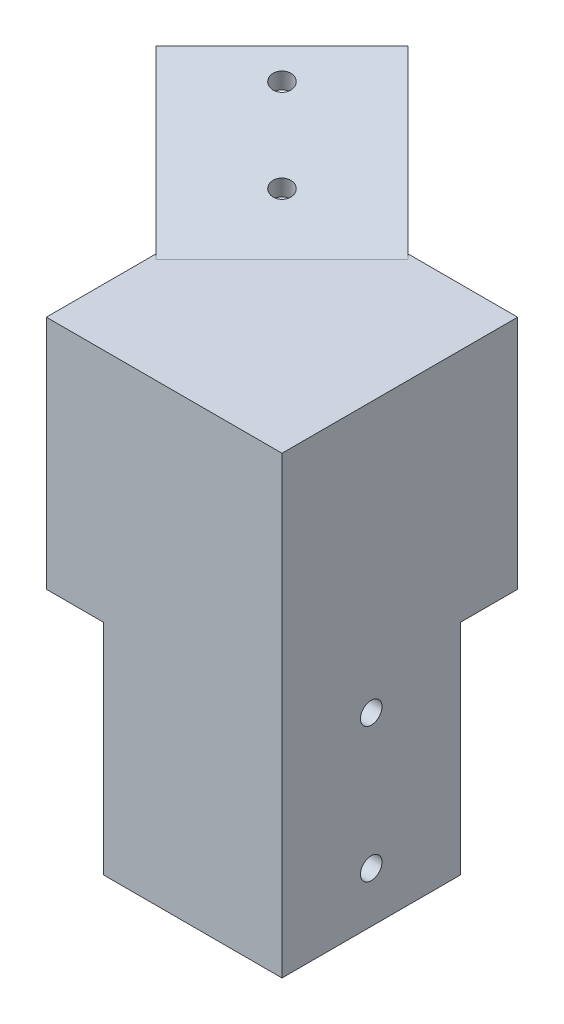
SolidWorks part; units mm, degrees
ref_plane "前视基准面" through (0, 0, 0) normal (0, 0, 1) x (1, 0, 0)
ref_plane "上视基准面" through (0, 0, 0) normal (0, 1, 0) x (1, 0, 0)
ref_plane "右视基准面" through (0, 0, 0) normal (1, 0, 0) x (0, 0, -1)
other "Configuration Table"
sketch "草图2" plane through (0, 0, 0) normal (1, 0, 0) x (0, 0, -1)
  line L0 (0, 0) -> (-60, 0)
  line L1 (-60, 0) -> (-60, -20)
  dimension "D1" = 60
  dimension "D2" = 20
ref_plane "基准面1" through (0, 0, 60) normal (0, 0, 1) x (1, 0, 0)
sketch "草图3" plane through (0, 0, 60) normal (0, 0, 1) x (1, 0, 0)
  line L0 (0, -20) -> (60, -20)
  line L1 (0, 0) -> (0, -20) construction
  line L2 (0, 0) -> (50000, 0) construction
  dimension "D1" = 20
  dimension "D2" = 60
sketch3d "3D草图1"
  line L0 (0, 0, 0) -> (60, -20, 60)
  line L1 (0, 0, 0) -> (0, -20, 0)
  dimension "D1" = 20
sketch "草图4" plane through (0, 0, 0) normal (0, 1, 0) x (1, 0, 0)
  line L1 (-10.25, 10.25) -> (10.25, 10.25)
  line L2 (-10.25, 10.25) -> (-10.25, -10.25)
  line L3 (-10.25, -10.25) -> (10.25, -10.25)
  line L4 (10.25, 10.25) -> (10.25, -10.25)
  line L5 (-10.25, 10.25) -> (10.25, -10.25) construction
  line L6 (-10.25, -10.25) -> (10.25, 10.25) construction
  line L7 (-13.25, 13.25) -> (13.25, 13.25)
  line L8 (-13.25, 13.25) -> (-13.25, -13.25)
  line L9 (-13.25, -13.25) -> (13.25, -13.25)
  line L10 (13.25, 13.25) -> (13.25, -13.25)
  line L11 (-13.25, 13.25) -> (13.25, -13.25) construction
  line L12 (-13.25, -13.25) -> (13.25, 13.25) construction
  point P0 (0, 0)
  point P6 (0, 0)
  dimension "D1" = 20.5
  dimension "D2" = 3
extrude "凸台-拉伸1" add sketch "草图4" against normal blind 50
ref_plane "基准面2" through (0, 0, 0) normal (0.6882, -0.2294, 0.6882) x (0.7255, 0.2176, -0.6529)
sketch "草图5" plane through (0, 0, 0) normal (0.6882, -0.2294, 0.6882) x (0.7255, 0.2176, -0.6529)
  line L1 (-7.6985, 12.2824) -> (12.2824, 7.6985)
  line L2 (-7.6985, 12.2824) -> (-12.2824, -7.6985)
  line L3 (-12.2824, -7.6985) -> (7.6985, -12.2824)
  line L4 (12.2824, 7.6985) -> (7.6985, -12.2824)
  line L5 (-7.6985, 12.2824) -> (7.6985, -12.2824) construction
  line L6 (-12.2824, -7.6985) -> (12.2824, 7.6985) construction
  line L7 (-9.9517, 15.8773) -> (15.8773, 9.9517)
  line L8 (-9.9517, 15.8773) -> (-15.8773, -9.9517)
  line L9 (-15.8773, -9.9517) -> (9.9517, -15.8773)
  line L10 (15.8773, 9.9517) -> (9.9517, -15.8773)
  line L11 (-9.9517, 15.8773) -> (9.9517, -15.8773) construction
  line L12 (-15.8773, -9.9517) -> (15.8773, 9.9517) construction
  line L14 (-18.2639, 4.19) -> (-18.2639, -48.5146)
  line L15 (-18.2639, 4.19) -> (-18.2639, -48.5146)
  line L16 (-4.7095, -51.6242) -> (18.2639, -4.19)
  line L17 (-4.7095, -51.6242) -> (18.2639, -4.19)
  line L18 (-4.7095, -51.6242) -> (-18.2639, -48.5146)
  point P0 (0, 0)
  point P6 (0, 0)
  dimension "D1" = 20.5
  dimension "D2" = 3
extrude "凸台-拉伸2" add sketch "草图5" against normal blind 50 contours L10 L7 L8 L9 L1 L4 L3 L2 region at (2.0766, 12.4595, 2.0766)
sketch "草图6" plane through (0, 0, 0) normal (0, 1, 0) x (1, 0, 0)
  line L7 (13.25, -13.25) -> (-21.75, -13.25)
  line L8 (-21.75, -13.25) -> (-21.75, 3.0117)
  line L9 (-41.6321, 22.8938) -> (-7.2197, -11.5186) construction
  line L10 (-21.75, 3.0117) -> (-3.0117, 21.75)
  line L11 (-27.1926, 45.931) -> (5.4883, 13.25) construction
  line L12 (-3.0117, 21.75) -> (13.25, 21.75)
  line L13 (13.25, 21.75) -> (13.25, -13.25)
  dimension "D1" = 35
extrude "凸台-拉伸3" add sketch "草图6" along normal mid plane 35
extrude "切除-拉伸1" cut sketch "草图4<2>" against normal through all contours L4 L1 L2 L3 region at (0, 0, 0)
sketch "草图4<2>" plane through (0, 0, 0) normal (0, 1, 0) x (1, 0, 0) same geometry as "草图4"
extrude "切除-拉伸2" cut sketch "草图5<2>" against normal through all contours L4 L1 L2 L3 region at (0, 0, 0)
sketch "草图5<2>" plane through (0, 0, 0) normal (0.6882, -0.2294, 0.6882) x (0.7255, 0.2176, -0.6529) same geometry as "草图5"
sketch "草图7" plane through (2.1494, 12.8966, 2.1494) normal (0.1622, 0.9733, 0.1622) x (0.9868, -0.16, -0.0267)
  line L0 (-34.8743, 35.8299) -> (34816.0025, -35770.0422) construction
  line L1 (-44.3692, 26.5882) -> (-25.3794, 45.0716) construction
  circle A0 centre (-31.3869, 32.2469) radius 1.5
  circle A1 centre (-20.9246, 21.498) radius 1.5
  point P4 (-34.8743, 35.8299)
  dimension "D1" = 15
  dimension "D2" = 5
  dimension "D3" = 3
extrude "切除-拉伸3" cut sketch "草图7" against normal through all
sketch "草图8" plane through (-13.25, 0, 0) normal (-1, 0, 0) x (0, 0, 1)
  line L0 (0, 0) -> (0, -50000) construction
  line L1 (-11.5117, -17.5) -> (13.25, -17.5) construction
  circle A0 centre (0, -22.5) radius 1.6
  circle A1 centre (0, -42.5) radius 1.6
  dimension "D1" = 20
  dimension "D2" = 3.2
  dimension "D3" = 5
extrude "切除-拉伸4" cut sketch "草图8" against normal through all
